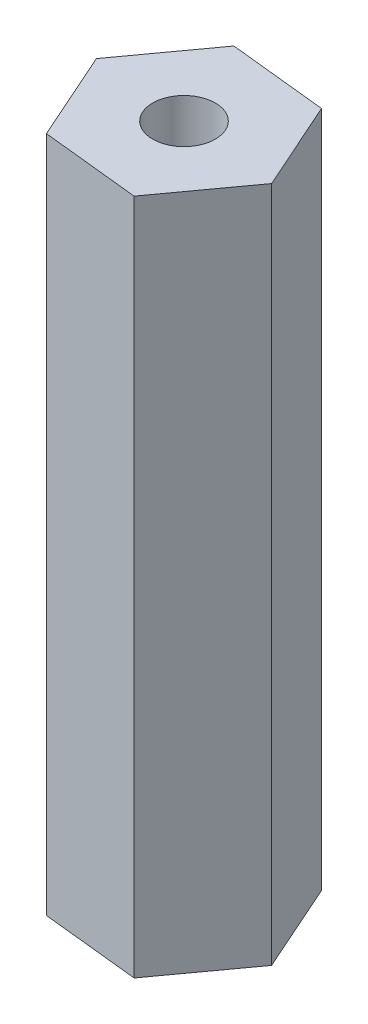
SolidWorks part; units mm, degrees
ref_plane "Front Plane" through (0, 0, 0) normal (0, 0, 1) x (1, 0, 0)
ref_plane "Top Plane" through (0, 0, 0) normal (0, 1, 0) x (1, 0, 0)
ref_plane "Right Plane" through (0, 0, 0) normal (1, 0, 0) x (0, 0, -1)
sketch "Sketch1" plane through (0, 0, 0) normal (0, 1, 0) x (1, 0, 0)
  line L1 (2.3073, 3.1766) -> (-1.5974, 3.5865)
  line L2 (-1.5974, 3.5865) -> (-3.9047, 0.4099)
  line L3 (-3.9047, 0.4099) -> (-2.3073, -3.1766)
  line L4 (-2.3073, -3.1766) -> (1.5974, -3.5865)
  line L5 (1.5974, -3.5865) -> (3.9047, -0.4099)
  line L6 (3.9047, -0.4099) -> (2.3073, 3.1766)
  circle A0 centre (0, 0) radius 1.25
  circle A1 centre (0, 0) radius 3.4001 construction
extrude "Boss-Extrude1" add sketch "Sketch1" along normal blind 27
